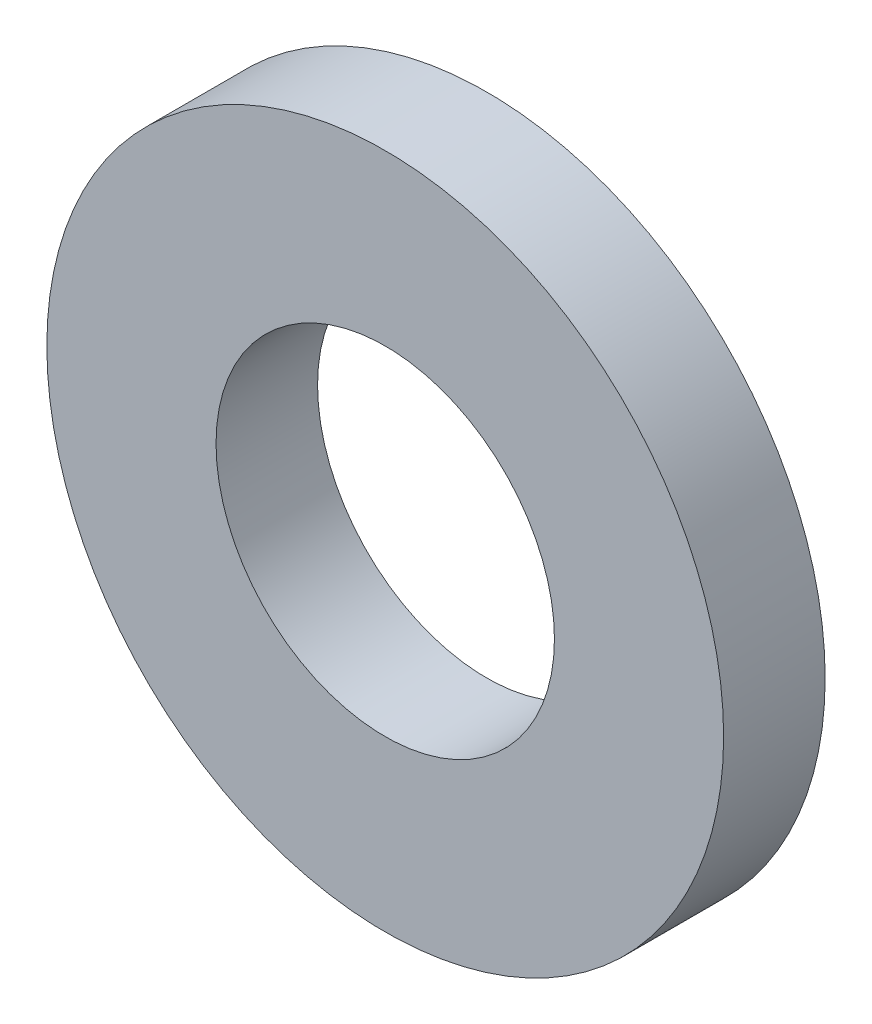
SolidWorks part; units mm, degrees
material "Cast Stainless Steel"
ref_plane "Front Plane" through (0, 0, 0) normal (0, 0, 1) x (1, 0, 0)
ref_plane "Top Plane" through (0, 0, 0) normal (0, 1, 0) x (1, 0, 0)
ref_plane "Right Plane" through (0, 0, 0) normal (1, 0, 0) x (0, 0, -1)
sketch "Sketch1" plane through (0, 0, 0) normal (0, 0, 1) x (1, 0, 0)
  circle A0 centre (0, 0) radius 3
  circle A1 centre (0, 0) radius 1.5
  dimension "OD" = 6
  dimension "ID1" = 3
extrude "Boss-Extrude1" add sketch "Sketch1" along normal blind 0.9
ref_axis "Center Axis 1" through (0, 0, 0.9) along (0, 0, -1)
ref_plane "Contact Plane 1" through (0, 0, 0.9) normal (0, 0, 1) x (1, 0, 0)
ref_plane "Contact Plane 2" through (0, 0, 0) normal (0, 0, -1) x (-1, 0, 0)
